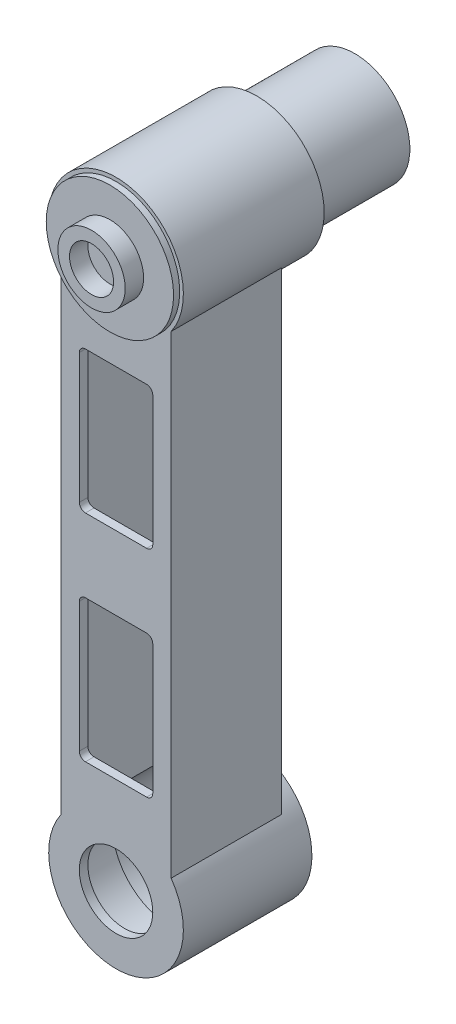
SolidWorks part; units mm, degrees
material "Cast Stainless Steel"
ref_plane "Front Plane" through (0, 0, 0) normal (0, 0, 1) x (1, 0, 0)
ref_plane "Top Plane" through (0, 0, 0) normal (0, 1, 0) x (1, 0, 0)
ref_plane "Right Plane" through (0, 0, 0) normal (1, 0, 0) x (0, 0, -1)
other "Center of Mass"
sketch "Sketch11" plane through (0, 0, 0) normal (0, 0, 1) x (1, 0, 0)
  line L0 (0, 450) -> (0, 0) construction
  line L1 (45, 31.6228) -> (45, 418.3772)
  line L4 (-45, 31.6228) -> (-45, 418.3772)
  circle A0 centre (0, 0) radius 55
  circle A1 centre (0, 450) radius 55
  dimension "D1" = 110
  dimension "D2" = 110
  dimension "D3" = 45
  dimension "D4" = 45
  dimension "D5" = 450
extrude "Boss-Extrude5" add sketch "Sketch11" along normal blind 90 contours A1 L4 A0 L1 | L0 A1 L4 A0 | A1 | A0 region at (22.9648, 225, 0) region at (-22.9648, 225, 0) region at (-24.6378, 402.5734, 0) region at (24.6378, 47.4266, 0)
extrude "Boss-Extrude6" add sketch "Sketch11<3>" along normal blind 115 contours A1 region at (0, 450, 0)
sketch "Sketch11<3>" plane through (0, 0, 0) normal (0, 0, 1) x (1, 0, 0) same geometry as "Sketch11"
extrude "Boss-Extrude7" add sketch "Sketch11<4>" along normal blind 105 contours A0 region at (0, 0, 0)
sketch "Sketch11<4>" plane through (0, 0, 0) normal (0, 0, 1) x (1, 0, 0) same geometry as "Sketch11"
sketch "Sketch13" plane through (0, 0, 90) normal (0, 0, 1) x (1, 0, 0)
  line L2 (7.6389, 82) -> (7.6389, 54.4669)
  line L3 (7.6389, 54.4669) -> (-7.6389, 54.4669)
  line L4 (-7.6389, 82) -> (-7.6389, 54.4669)
  arc A1 (7.6389, 82) -> (-7.6389, 82) centre (0, 82) ccw
  arc A2 (45, 31.6228) -> (-45, 31.6228) centre (0, 0) ccw construction
extrude "Boss-Extrude8" add sketch "Sketch13" along normal blind 15
sketch "Sketch17" plane through (0, 0, 115) normal (0, 0, 1) x (1, 0, 0)
  circle A0 centre (0, 450) radius 45
extrude "Boss-Extrude9" add sketch "Sketch17" along normal blind 80
sketch "Sketch18" plane through (0, 0, 0) normal (0, 0, -1) x (-1, 0, 0)
  circle A0 centre (0, 450) radius 52
extrude "Boss-Extrude10" add sketch "Sketch18" along normal blind 5
sketch "Sketch19" plane through (0, 0, -5) normal (0, 0, -1) x (-1, 0, 0)
  circle A0 centre (0, 450) radius 37.5
  circle A1 centre (0, 450) radius 27.5
  circle A2 centre (0, 450) radius 18
extrude "Boss-Extrude12" add sketch "Sketch19" along normal blind 15 contours A2 | A1
ref_plane "Plane1" through (0, 0, 167.63) normal (0, 0, -1) x (-1, 0, 0)
move or copy body "Body-Move/Copy2" bodies to move or copy 113 copy no rotation origin (0, 0, 0) rotation axis (0, 1, 0) rotation angle 180
sketch "Sketch28" plane through (0, 0, -105) normal (0, 0, -1) x (-1, 0, 0)
  circle A0 centre (0, 0) radius 52
  dimension "D1" = 104
extrude "Cut-Extrude2" cut sketch "Sketch28" against normal blind 60
ref_plane "Plane2" through (0, 0, 10) normal (0, 0, 1) x (1, 0, 0)
sketch "Sketch29" plane through (0, 0, 0) normal (0, 0, 1) x (1, 0, 0)
  line L0 (-30, 255) -> (-30, 195) construction
  line L1 (-25, 195) -> (25, 195)
  line L2 (-30, 190) -> (-30, 84)
  line L3 (-25, 79) -> (25, 79)
  line L4 (30, 190) -> (30, 84)
  line L5 (-25, 371) -> (25, 371)
  line L6 (45, 31.6228) -> (45, 418.3772)
  line L7 (-45, 418.3772) -> (-45, 31.6228)
  line L8 (45, 31.6228) -> (45, 418.3772)
  line L9 (-45, 418.3772) -> (-45, 31.6228)
  line L10 (-30, 366) -> (-30, 260)
  line L11 (-25, 255) -> (25, 255)
  line L12 (30, 366) -> (30, 260)
  line L13 (-30, 225) -> (103.3616, 225) construction
  line L14 (0, 450) -> (0, 0) construction
  arc A0 (25, 255) -> (30, 260) centre (25, 260) ccw
  arc A1 (-25, 255) -> (-30, 260) centre (-25, 260) cw
  arc A2 (-45, 31.6228) -> (45, 31.6228) centre (0, 0) ccw
  arc A3 (45, 418.3772) -> (-45, 418.3772) centre (0, 450) ccw
  arc A4 (-45, 31.6228) -> (45, 31.6228) centre (0, 0) ccw
  arc A5 (45, 418.3772) -> (-45, 418.3772) centre (0, 450) ccw
  arc A6 (30, 366) -> (25, 371) centre (25, 366) ccw
  arc A7 (-30, 366) -> (-25, 371) centre (-25, 366) cw
  arc A8 (30, 84) -> (25, 79) centre (25, 84) cw
  arc A9 (-30, 84) -> (-25, 79) centre (-25, 84) ccw
  arc A10 (30, 190) -> (25, 195) centre (25, 190) ccw
  arc A11 (-30, 190) -> (-25, 195) centre (-25, 190) cw
  point P26 (-30, 371)
  point P29 (30, 79)
  point P32 (-30, 79)
  dimension "D5" = 5
  dimension "D6" = 5
  dimension "D2" = 116
  dimension "D3" = 60
  dimension "D4" = 60
  dimension "D1" = 0
extrude "Cut-Extrude3" cut sketch "Sketch29" against normal offset from surface (80 mm away) 10 contours A7 L10 A1 L11 A0 L12 A6 L5 | A11 L2 A9 L3 A8 L4 A10 L1 region at (0, 137, 0) region at (0, 313, 0) up to face at (0, 145.6191, -90)
ref_plane "Plane3" through (0, 0, 10) normal (0, 0, 1) x (1, 0, 0)
sketch "Sketch30" plane through (0, 0, 10) normal (0, 0, 1) x (1, 0, 0)
  line L0 (38, 29.3258) -> (38, 420.6742)
  line L1 (-38, 420.6742) -> (-38, 29.3258)
  line L2 (45, 31.6228) -> (45, 418.3772)
  line L3 (-45, 418.3772) -> (-45, 31.6228)
  line L4 (45, 31.6228) -> (45, 418.3772)
  line L5 (-45, 418.3772) -> (-45, 31.6228)
  arc A0 (-38, 29.3258) -> (38, 29.3258) centre (0, 0) ccw
  arc A1 (38, 420.6742) -> (-38, 420.6742) centre (0, 450) ccw
  arc A2 (-45, 31.6228) -> (45, 31.6228) centre (0, 0) ccw
  arc A3 (45, 418.3772) -> (-45, 418.3772) centre (0, 450) ccw
  arc A4 (-45, 31.6228) -> (45, 31.6228) centre (0, 0) ccw
  arc A5 (45, 418.3772) -> (-45, 418.3772) centre (0, 450) ccw
  dimension "D1" = 0
  dimension "D2" = 7
extrude "Cut-Extrude5" cut sketch "Sketch30" against normal up to surface (90 mm away) from offset 17 contours L0 A1 L1 A0 up to face at (0, 313, -80) offset against normal yes
sketch "Sketch31" plane through (0, 0, 0) normal (0, 0, 1) x (1, 0, 0)
  line L2 (45, 31.6228) -> (45, 418.3772)
  line L3 (-45, 418.3772) -> (-45, 31.6228)
  line L4 (45, 31.6228) -> (45, 418.3772)
  line L5 (-45, 418.3772) -> (-45, 31.6228)
  circle A0 centre (0, 0) radius 30
  arc A2 (-45, 31.6228) -> (45, 31.6228) centre (0, 0) ccw
  arc A3 (45, 418.3772) -> (-45, 418.3772) centre (0, 450) ccw
  arc A4 (-45, 31.6228) -> (45, 31.6228) centre (0, 0) ccw
  arc A5 (45, 418.3772) -> (-45, 418.3772) centre (0, 450) ccw
  dimension "D2" = 60
  dimension "D1" = 0
extrude "Cut-Extrude6" cut sketch "Sketch31" against normal through all contours A0 region at (0, 0, 0)
